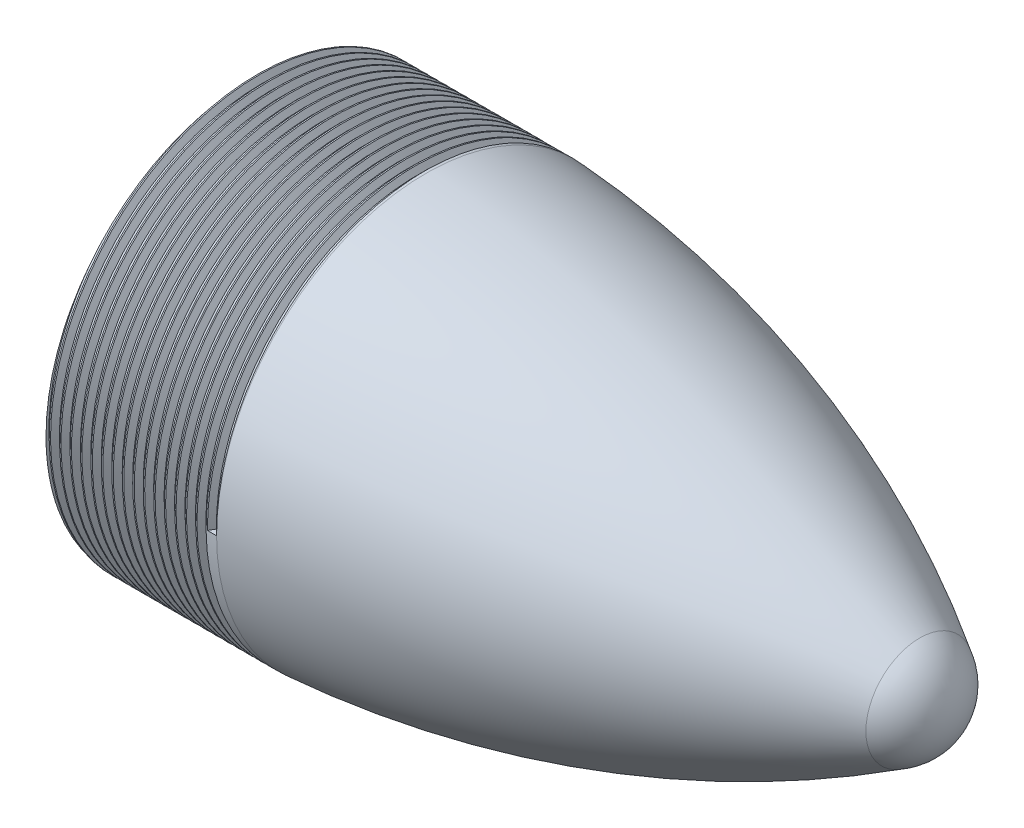
SolidWorks part; units mm, degrees
material "Aleación 2014"
ref_plane "Alzado" through (0, 0, 0) normal (0, 0, 1) x (1, 0, 0)
ref_plane "Planta" through (0, 0, 0) normal (0, 1, 0) x (1, 0, 0)
ref_plane "Vista lateral" through (0, 0, 0) normal (1, 0, 0) x (0, 0, -1)
sketch "Croquis1" plane through (0, 0, 0) normal (0, 1, 0) x (1, 0, 0)
  line L6 (-45, 0) -> (68.4897, 0) construction
  line L8 (55, 0) -> (47, 0) construction
  line L9 (-20, 0) -> (55.6179, 0)
  line L13 (-45, 30) -> (-20, 30)
  line L14 (-45, 25) -> (-45, 30)
  arc A4 (55.6179, 0) -> (50.8303, 7.7199) centre (47, 0) ccw
  arc A5 (-20, 30) -> (50.8303, 7.7199) centre (-29.7404, -124.6936) cw
  arc A6 (-20, 0) -> (-45, 25) centre (-45, 0) ccw
  point P0 (0, 0)
  dimension "D3" = 155
  dimension "D6" = 8
  dimension "D2" = 75
revolve "Revolución2" add sketch "Croquis1" angle 360 about L6
thread "Rosca2" pitch 1.5 method cut profile "Perfil de rosca2" start angle 0, offset 0, length 32, pitch 1.5, diameter 60
ref_plane "Plano2" through (-20, 0, 30) normal (0, -1, 0) x (0, 0, 1)
sketch "Perfil de rosca2" plane through (-20, 0, 30) normal (0, -1, 0) x (0, 0, 1)
  line L0 (0, 0) -> (0, 1.5) construction
  line L11 (0, 0) -> (0, 1.3125)
  line L12 (0, 1.3125) -> (-0.8119, 0.8437)
  line L13 (-0.8119, 0.8437) -> (-0.8119, 0.4687)
  line L15 (-0.8119, 0.4687) -> (0, 0)
  line L17 (-0.8119, 0.6562) -> (0, 0.6562) construction
  point P2 (0, 0)
  dimension "Pitch" = 1.5
  dimension "Profile_Angle" = 60
  dimension "Profile_Land" = 0.375
  dimension "Profile_Height" = 0.8119
